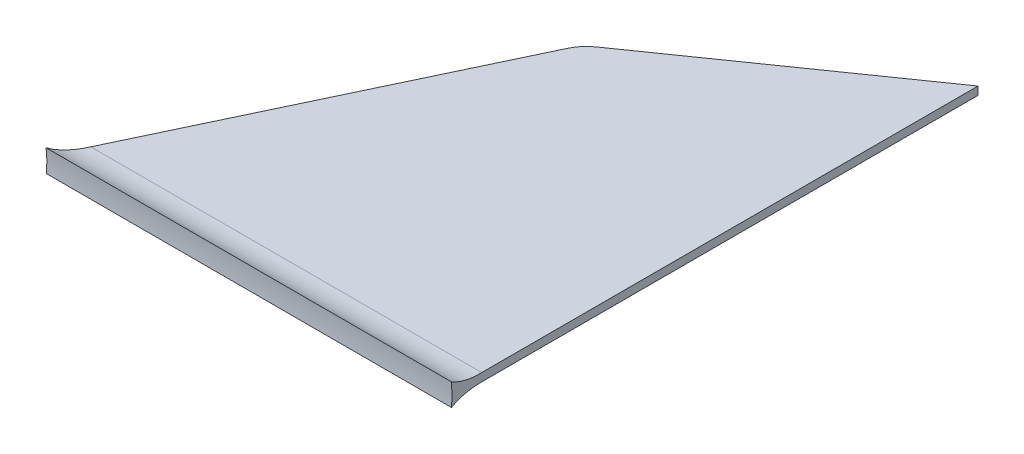
SolidWorks part; units mm, degrees
material "Plástico personalizado"
ref_plane "Plano frontal" through (0, 0, 0) normal (0, 0, 1) x (1, 0, 0)
ref_plane "Plano superior" through (0, 0, 0) normal (0, 1, 0) x (1, 0, 0)
ref_plane "Plano direito" through (0, 0, 0) normal (1, 0, 0) x (0, 0, -1)
sketch "Esboço1" plane through (0, 0, 0) normal (0, 1, 0) x (1, 0, 0)
  line L0 (0, 0) -> (100.1, 0)
  line L1 (100.1, 0) -> (100.1, 130.2)
  line L2 (100.1, 130.2) -> (42.5645, 90)
  line L3 (42.5645, 90) -> (0, 0)
  point P3 (42.5645, 98.7523)
  dimension "D1" = 100.1
  dimension "D2" = 130.2
  dimension "D3" = 90
  dimension "D4" = 90
extrude "Ressalto-extrusão1" add sketch "Esboço1" along normal blind 2
fillet "Filete1" radius 10 1 edges at (42.5645, 1, -90)
sketch "Esboço2" plane through (0, 0, 0) normal (0, -1, 0) x (-1, 0, 0)
  line L0 (-100.1, 0) -> (-100.1, 7.846)
  line L1 (-100.1, 0) -> (-100.1, 130.2) construction
  line L2 (-100.1, 7.846) -> (-3.7107, 7.846)
  line L3 (-41.429, 87.5991) -> (0, 0) construction
  line L4 (-3.7107, 7.846) -> (0, 0)
  line L5 (0, 0) -> (-100.1, 0)
extrude "Ressalto-extrusão2" add sketch "Esboço2" along normal blind 2 and the other way blind 4
sketch "Esboço4" plane through (100.1, 0, 0) normal (1, 0, 0) x (0, 0, -1)
  line L0 (0, 4) -> (7.846, 4)
  line L1 (7.846, 4) -> (7.846, 2)
  line L2 (7.846, 0) -> (7.846, -2)
  line L3 (7.846, -2) -> (0, -2)
  spline S0 degree 2 poles (7.846, 2) (3.1403, 1.9039) (0, 4) knots 0 0 0 1 1 1
  spline S1 degree 2 poles (7.846, 0) (3.1069, 0.0091) (0, -2) knots 0 0 0 1 1 1
extrude "Corte-extrusão1" cut sketch "Esboço4" against normal blind 106
sketch "Esboço5" plane through (100.1, 0, 0) normal (1, 0, 0) x (0, 0, -1)
  line L0 (0, 4) -> (0, -2) construction
  circle A0 centre (-32, 0.7324) radius 32.5
  dimension "D1" = 32
extrude "Corte-extrusão2" cut sketch "Esboço5" against normal blind 106
